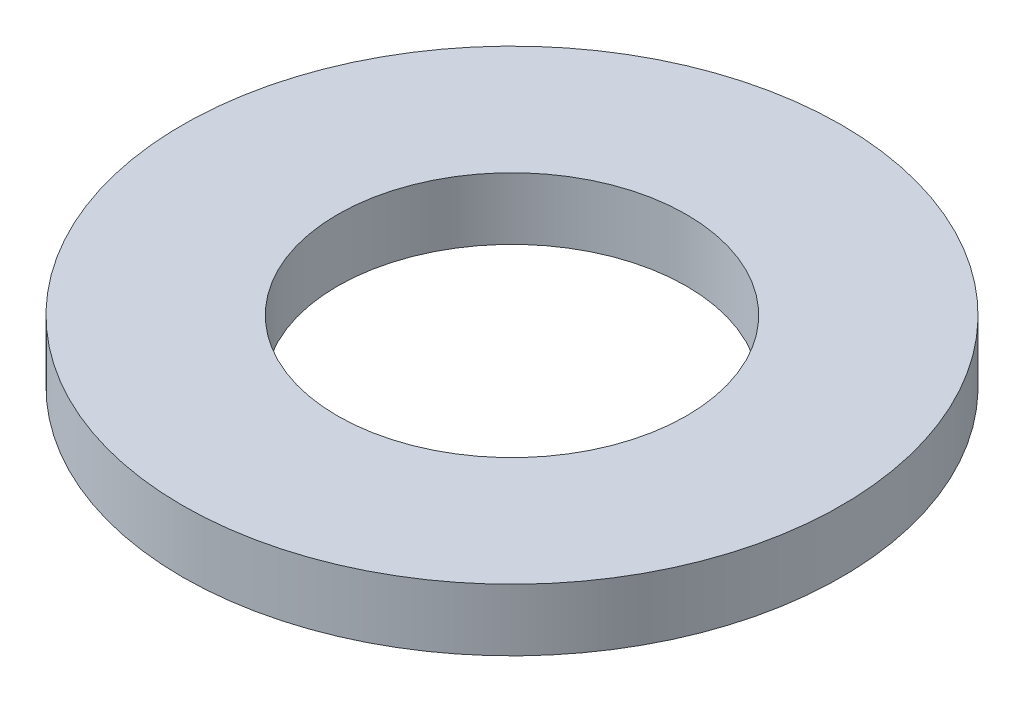
SolidWorks part; units mm, degrees
ref_plane "Front Plane" through (0, 0, 0) normal (0, 0, 1) x (1, 0, 0)
ref_plane "Top Plane" through (0, 0, 0) normal (0, 1, 0) x (1, 0, 0)
ref_plane "Right Plane" through (0, 0, 0) normal (1, 0, 0) x (0, 0, -1)
sketch "BodySke" plane through (0, 0, 0) normal (0, 0, -1) x (1, 0, 0)
  line L0 (0, 0) -> (0, 7.8986) construction
  line L2 (4.5, 1.6) -> (8.5, 1.6)
  line L3 (4.5, 1.6) -> (4.5, 0)
  line L4 (4.5, 0) -> (8.5, 0)
  line L5 (8.5, 1.6) -> (8.5, 0)
  dimension "Inner_dia" = 9
  dimension "Outer_dia" = 17
  dimension "Thickness" = 1.6
revolve "BaseBody" add sketch "BodySke" angle 360 about L0
